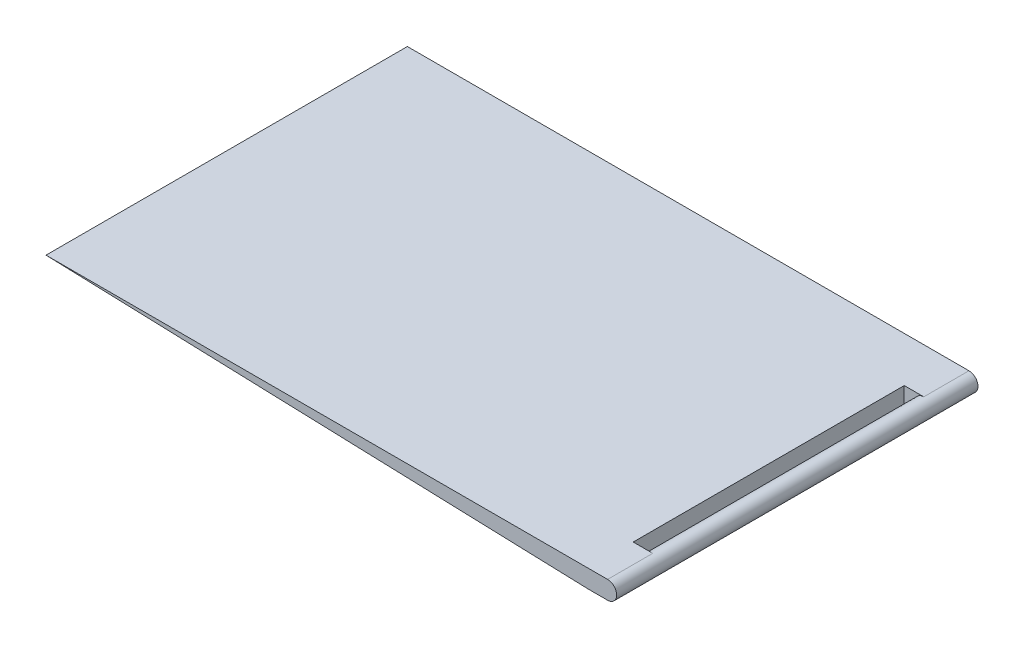
SolidWorks part; units mm, degrees
ref_plane "Plan de face" through (0, 0, 0) normal (0, 0, 1) x (1, 0, 0)
ref_plane "Plan de dessus" through (0, 0, 0) normal (0, 1, 0) x (1, 0, 0)
ref_plane "Plan de droite" through (0, 0, 0) normal (1, 0, 0) x (0, 0, -1)
sketch "Esquisse1" plane through (0, 0, 0) normal (0, 0, 1) x (1, 0, 0)
  circle A0 centre (0, 0) radius 1
extrude "Boss.-Extru.1" add sketch "Esquisse1" along normal blind 20 and the other way blind 20
sketch "Esquisse2" plane through (0, 0, 20) normal (0, 0, 1) x (1, 0, 0)
  line L1 (-2.1634, -1) -> (-62.1634, 1)
  line L2 (-62.1634, 1) -> (-2.1634, 1)
  line L3 (-2.1634, 1) -> (-2.1634, -1)
extrude "Boss.-Extru.2" add sketch "Esquisse2" against normal up to surface (40 mm away) separate body up to face at (1, 0, -20)
sketch "Esquisse3" plane through (0, 0, 20) normal (0, 0, 1) x (1, 0, 0)
  line L0 (-2.1634, 1) -> (0, 1)
  line L1 (0, 1) -> (0, -1)
  line L2 (0, -1) -> (-2.1634, -1)
  line L3 (-2.1634, -1) -> (-2.1634, 1)
  circle A0 centre (0, 0) radius 1 construction
extrude "Boss.-Extru.3" add sketch "Esquisse3" against normal blind 5
sketch "Esquisse4" plane through (0, 0, -20) normal (0, 0, -1) x (-1, 0, 0)
  line L0 (2.1634, 1) -> (0, 1)
  line L1 (0, 1) -> (2.1634, 1) construction
  line L2 (0, 1) -> (0, -1)
  line L3 (0, -1) -> (2.1634, -1)
  line L4 (2.1634, -1) -> (2.1634, 1)
  circle A0 centre (0, 0) radius 1 construction
extrude "Boss.-Extru.4" add sketch "Esquisse4" against normal blind 5
